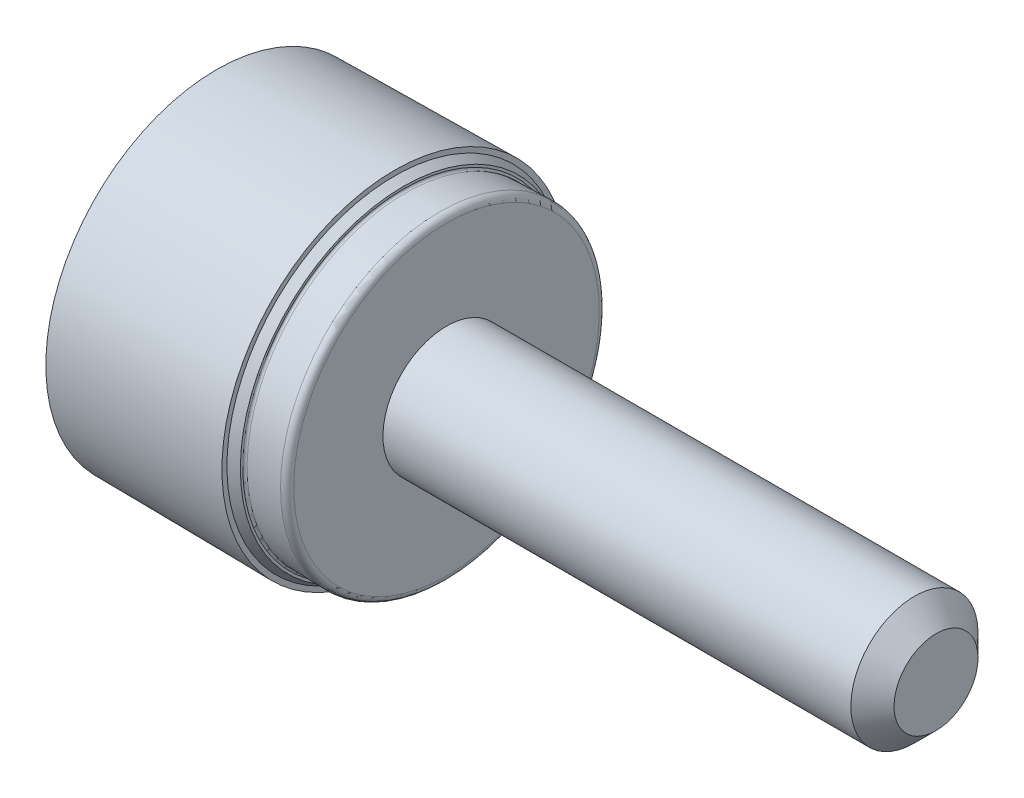
SolidWorks part; units mm, degrees
ref_plane "Front Plane" through (0, 0, 0) normal (0, 0, 1) x (1, 0, 0)
ref_plane "Top Plane" through (0, 0, 0) normal (0, 1, 0) x (1, 0, 0)
ref_plane "Right Plane" through (0, 0, 0) normal (1, 0, 0) x (0, 0, -1)
sketch "Sketch1" plane through (0, 0, 0) normal (0, 0, 1) x (1, 0, 0)
  line L0 (9.1281, 0) -> (-9.1281, 0) construction
  line L1 (9.1281, 1.7526) -> (9.1281, -1.7526) construction
  line L2 (-9.1281, 4.7625) -> (-9.1281, -4.7625) construction
  line L3 (-4.3656, 4.7625) -> (-4.3656, -4.7625) construction
  line L4 (9.0785, 1.8385) -> (9.8723, 1.8385) construction
  line L5 (9.0785, 1.8385) -> (9.4754, 1.1511) construction
  line L6 (9.4754, 1.1511) -> (9.8723, 1.8385) construction
  line L7 (9.4754, 1.8385) -> (9.4754, 1.7526) construction
  line L8 (9.4754, 1.1511) -> (9.4754, 1.237) construction
  line L9 (9.4258, 1.237) -> (9.525, 1.237) construction
  line L10 (9.1281, 1.7526) -> (9.8227, 1.7526) construction
  line L12 (-5.5562, 4.3656) -> (-5.5562, -4.3656) construction
  point P2 (5.5562, -1.7526)
  point P20 (-8.4119, 0)
  point P23 (-5.5562, 0)
  dimension "Thread Size" = 3.5052
  dimension "Head Diameter" = 9.525
  dimension "Head Height" = 4.7625
  dimension "Length" = 13.4937
  dimension "Thread Pitch" = 0.7937
  dimension "D1" = 0.0992
  dimension "D2" = 3.5719
  dimension "Shoulder Diameter" = 8.7312
  dimension "D3" = 0.7162
  dimension "Knurled Head Height" = 3.5719
sketch "Sketch2" plane through (0, 0, 0) normal (1, 0, 0) x (0, 0, -1)
  line L0 (0, 4.3656) -> (0, -4.3656) construction
  line L1 (0, 1.604) -> (-1.3891, 0.802) construction
  line L2 (-1.3891, 0.802) -> (-1.3891, -0.802) construction
  line L3 (-1.3891, -0.802) -> (0, -1.604) construction
  line L4 (0, -1.604) -> (1.3891, -0.802) construction
  line L5 (1.3891, -0.802) -> (1.3891, 0.802) construction
  line L6 (1.3891, 0.802) -> (0, 1.604) construction
  circle A0 centre (0, 0) radius 4.7625 construction
  circle A1 centre (0, 0) radius 1.3891 construction
  dimension "Drive Size" = 2.7781
sketch "Sketch3" plane through (0, 0, 0) normal (0, 0, 1) x (1, 0, 0)
  line L0 (-10.7029, 2.8702) -> (-10.7029, 4.7085)
  line L1 (-10.7029, 4.7085) -> (-5.7944, 4.7625)
  line L2 (-4.3656, 0) -> (-9.1281, 0) construction
  line L3 (-5.5562, 4.4269) -> (-5.5562, 4.493)
  line L6 (-9.1281, 4.7625) -> (-9.1281, -4.7625) construction
  line L7 (-5.6229, 2.8702) -> (-5.6229, 1.5756)
  line L8 (-9.1281, 0) -> (9.1281, 0) construction
  line L9 (-5.6229, 1.5756) -> (-4.3656, 1.5756)
  line L10 (-10.7029, 2.8702) -> (-5.6229, 2.8702)
  line L11 (-5.495, 4.3672) -> (-4.5494, 4.392)
  line L12 (-4.3656, 4.7625) -> (-4.3656, -4.7625) construction
  line L13 (-4.3656, 4.213) -> (-4.3656, 1.5756)
  line L14 (-8.1629, 2.8702) -> (-8.1629, 3.0472) construction
  line L15 (-4.9943, 1.5756) -> (-4.9943, 1.7526) construction
  line L18 (-8.89, 4.571) -> (-5.5562, 4.6292) construction
  line L19 (-5.5562, 4.3656) -> (-5.5562, -4.3656) construction
  line L20 (-5.7944, 4.7625) -> (-5.7944, 4.625)
  line L23 (-5.7944, 4.625) -> (-5.5562, 4.493)
  line L24 (-5.5562, 4.6292) -> (-5.5562, 4.7625) construction
  line L28 (-5.5562, 4.7625) -> (-5.7944, 4.7625) construction
  line L30 (-5.5562, 4.4958) -> (-5.5562, 4.6292) construction
  arc A0 (-4.5494, 4.392) -> (-4.3656, 4.213) centre (-4.5447, 4.213) cw
  arc A1 (-5.495, 4.3672) -> (-5.5562, 4.4269) centre (-5.4966, 4.4269) cw
  point P25 (-4.3656, 4.3968)
  point P40 (-5.5562, 4.3656)
  dimension "D3" = 0.1791
  dimension "D8" = 0.0597
  dimension "SHCS Head Dia" = 5.7404
  dimension "D1" = 5.08
revolve "Revolve1" add sketch "Sketch3" angle 360 about L8
sketch "Sketch4" plane through (0, 0, 0) normal (0, 0, 1) x (1, 0, 0)
  line L0 (-10.7029, 2.8702) -> (-5.6229, 2.8702)
  line L1 (-5.6229, 2.8702) -> (-5.6229, 1.7526)
  line L2 (-5.6229, 1.7526) -> (9.1281, 1.7526)
  line L3 (9.1281, 1.7526) -> (9.1281, 0)
  line L4 (-10.7029, 2.8702) -> (-10.7029, 0)
  line L6 (-10.7029, 0) -> (9.1281, 0) construction
  line L7 (9.1281, 0) -> (-10.7029, 0)
  line L8 (-10.7029, 4.7085) -> (-10.7029, -4.7085) construction
  line L9 (-10.7029, 4.7085) -> (-10.7029, -4.7085) construction
  point P12 (0, 0)
  dimension "D1" = 14.751
revolve "Revolve2" add sketch "Sketch4" angle 360 about L6
sketch "Sketch5" plane through (-10.7029, 0, 0) normal (-1, 0, 0) x (0, 0, 1)
  line L0 (0, 1.604) -> (1.3891, 0.802) construction
  line L1 (1.3891, 0.802) -> (1.3891, -0.802) construction
  line L2 (1.3891, -0.802) -> (0, -1.604) construction
  line L3 (0, -1.604) -> (-1.3891, -0.802) construction
  line L4 (-1.3891, -0.802) -> (-1.3891, 0.802) construction
  line L5 (-1.3891, 0.802) -> (0, 1.604) construction
  line L6 (0, 1.604) -> (1.3891, 0.802)
  line L7 (1.3891, 0.802) -> (1.3891, -0.802)
  line L8 (1.3891, -0.802) -> (0, -1.604)
  line L9 (0, -1.604) -> (-1.3891, -0.802)
  line L10 (-1.3891, -0.802) -> (-1.3891, 0.802)
  line L11 (-1.3891, 0.802) -> (0, 1.604)
chamfer "Chamfer2" distance 0.5953 angle 45 1 edges at (9.1281, -1.7526, 0)
ref_axis "Center Axis 1" through (-5.7944, 0, 0) along (-1, 0, 0)
ref_plane "Contact Plane 1" through (-4.3656, 0, 0) normal (1, 0, 0) x (0, 0, -1)
sketch "Sketch7" plane through (9.1281, 0, 0) normal (1, 0, 0) x (0, 0, -1)
  circle A0 centre (0, 0) radius 1.7526
  circle A2 centre (0, 0) radius 1.7526 construction
sketch "Sketch8" plane through (0, 0, 0) normal (0, 0, 1) x (1, 0, 0)
  line L0 (9.0785, 1.8385) -> (9.4754, 1.1511) construction
  line L1 (9.4754, 1.1511) -> (9.8723, 1.8385) construction
  line L2 (9.1281, 1.7526) -> (9.4258, 1.237)
  line L3 (9.525, 1.237) -> (9.8227, 1.7526)
  line L4 (9.4258, 1.237) -> (9.525, 1.237) construction
  line L5 (9.4258, 1.237) -> (9.525, 1.237)
  line L6 (9.1281, 1.7526) -> (9.8227, 1.7526) construction
  line L7 (9.1281, 1.7526) -> (9.8227, 1.7526)
  line L8 (9.4754, 1.7526) -> (9.4754, -1.7526) construction
  line L9 (9.4754, -1.7526) -> (8.6816, -1.7526) construction
  line L10 (8.6816, -1.7526) -> (7.8879, -1.7526) construction
  line L11 (7.8879, -1.7526) -> (7.0941, -1.7526) construction
  line L12 (7.0941, -1.7526) -> (6.3004, -1.7526) construction
  line L13 (6.3004, -1.7526) -> (5.5066, -1.7526) construction
  line L14 (5.5066, -1.7526) -> (4.7129, -1.7526) construction
  line L15 (4.7129, -1.7526) -> (3.9191, -1.7526) construction
  line L16 (9.0785, 1.8385) -> (9.8723, 1.8385) construction
  point P9 (9.4754, 0)
  point P21 (9.4754, -1.7526)
  point P22 (8.6816, -1.7526)
  point P23 (7.8879, -1.7526)
  point P24 (7.0941, -1.7526)
  point P25 (6.3004, -1.7526)
  point P26 (5.5066, -1.7526)
  point P27 (4.7129, -1.7526)
  point P28 (3.9191, -1.7526)
ref_plane "Plane1" through (-8.4119, 0, 0) normal (1, 0, 0) x (0, 0, -1)
sketch "Sketch9" plane through (-8.89, 0, 0) normal (-1, 0, 0) x (0, 0, 1)
  line L0 (-0.1421, 4.7604) -> (-0.0635, 4.5705)
  line L1 (0.1421, 4.7604) -> (0.0635, 4.5705)
  line L2 (-0.1835, 4.7049) -> (0, 0) construction
  line L3 (0.1835, 4.7049) -> (0, 0) construction
  circle A0 centre (0, 0) radius 4.571 construction
  circle A1 centre (0, 0) radius 4.7625 construction
  arc A2 (0.0635, 4.5705) -> (-0.0635, 4.5705) centre (0, 0) ccw
  arc A3 (0.12, 4.7069) -> (-0.12, 4.7069) centre (0, 0) ccw construction
  circle A4 centre (0, 0) radius 4.7085 construction
  arc A5 (0.1421, 4.7604) -> (-0.1421, 4.7604) centre (0, 0) ccw
  point P1 (-0.1835, 4.7049)
  point P2 (0.1835, 4.7049)
  dimension "D1" = 45
  dimension "D2" = 0.127
  dimension "D3" = 0.0635
  dimension "D4" = 0.0635
  dimension "D5" = 4.467
equation "\"D1@Sketch1\" = \"Thread Pitch@Sketch1\" / 8"
equation "\"D2@Sketch1\" = \"Thread Pitch@Sketch1\" * 4.5"
equation "\"D1@Chamfer2\" = \"Thread Pitch@Sketch1\" * .750"
equation "\"D3\" = \"D1@Sketch4\" -  ( \"Thread Pitch@Sketch1\" / 4 ) "
equation "\"D4\" = \"Thread Pitch@Sketch1\""
equation "\"D1\" =  ( 360 / \"D5@Sketch9\" ) "
equation "\"D3@Sketch9\" = \"D2@Sketch9\" / 2"
equation "\"D4@Sketch9\" = \"D3@Sketch9\""
equation "\"D3@Sketch3\"=\"D3@Sketch1\"/4"
equation "\"D1\" = \"SHCS Head Dia@Sketch3\" / 36"
equation "\"D8@Sketch3\"=\"D3@Sketch1\"/12"
equation "\"D1\" = \"SHCS Head Dia@Sketch3\" / 35"
equation "\"D1\" = \"Drive Size@Sketch2\" * 0.75"
